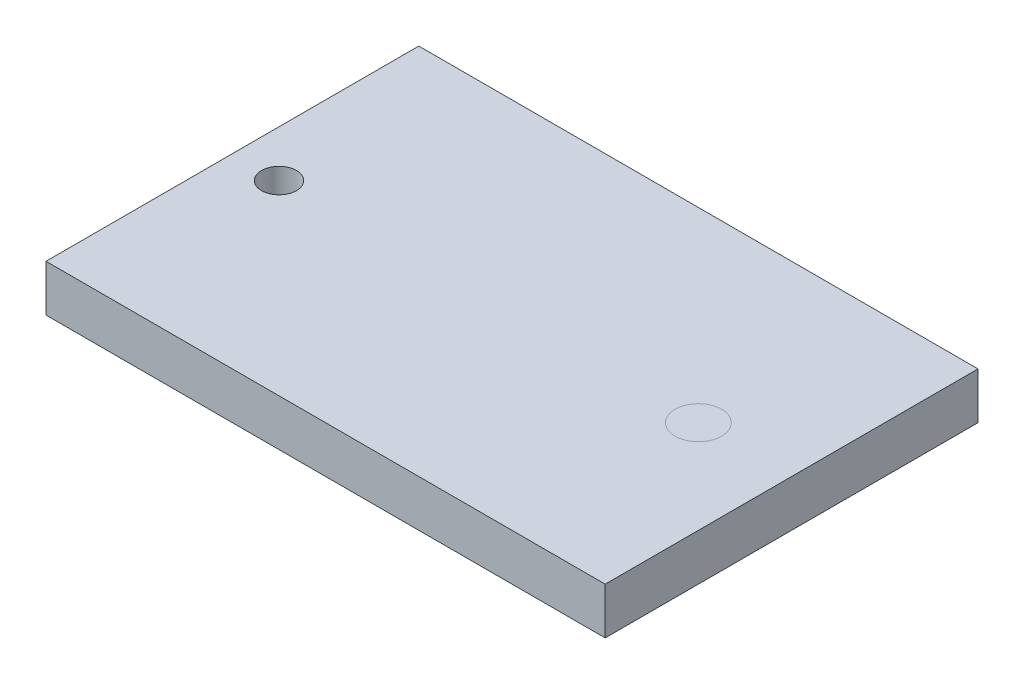
SolidWorks part; units mm, degrees
material "Acrylic (Medium-high impact)"
ref_plane "Front Plane" through (0, 0, 0) normal (0, 0, 1) x (1, 0, 0)
ref_plane "Top Plane" through (0, 0, 0) normal (0, 1, 0) x (1, 0, 0)
ref_plane "Right Plane" through (0, 0, 0) normal (1, 0, 0) x (0, 0, -1)
sketch "Sketch1" plane through (0, 0, 0) normal (0, 1, 0) x (1, 0, 0)
  line L1 (-38.1, 25.4) -> (38.1, 25.4)
  line L2 (-38.1, 25.4) -> (-38.1, -25.4)
  line L3 (-38.1, -25.4) -> (38.1, -25.4)
  line L4 (38.1, 25.4) -> (38.1, -25.4)
  line L5 (-38.1, 25.4) -> (38.1, -25.4) construction
  line L6 (-38.1, -25.4) -> (38.1, 25.4) construction
  circle A0 centre (-31.75, 0) radius 2.3813
  circle A1 centre (25.4, 0) radius 3.175
  point P0 (0, 0)
  dimension "D4" = 4.7625
  dimension "D5" = 6.35
  dimension "D6" = 12.7
  dimension "D7" = 25.4
  dimension "D8" = 25.4
  dimension "D1" = 76.2
  dimension "D2" = 50.8
  dimension "D3" = 6.35
extrude "Boss-Extrude1" add sketch "Sketch1" along normal blind 6.35 contours A1 | L4 L1 L2 L3 A1 A0 region at (-0.0625, 0, 0) region at (25.4, 0, 0)
split line "Split Line1"
sketch "Sketch1<3>" plane through (0, 0, 0) normal (0, 1, 0) x (1, 0, 0) same geometry as "Sketch1"
